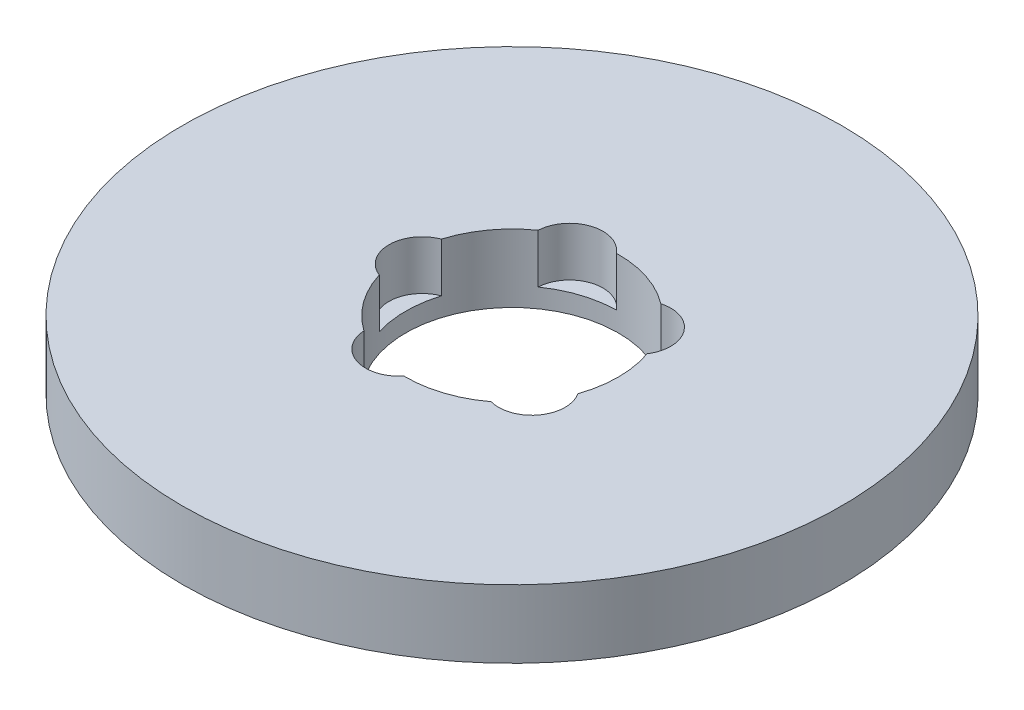
SolidWorks part; units mm, degrees
ref_plane "Front Plane" through (0, 0, 0) normal (0, 0, 1) x (1, 0, 0)
ref_plane "Top Plane" through (0, 0, 0) normal (0, 1, 0) x (1, 0, 0)
ref_plane "Right Plane" through (0, 0, 0) normal (1, 0, 0) x (0, 0, -1)
sketch "Sketch1" plane through (0, 0, 0) normal (0, 1, 0) x (1, 0, 0)
  circle A0 centre (0, 0) radius 77.5
  dimension "FLANGE_OD" = 155
extrude "Boss-Extrude1" add sketch "Sketch1" along normal blind 16
sketch "Sketch2" plane through (0, 0, 0) normal (0, 1, 0) x (1, 0, 0)
  circle A0 centre (0, 0) radius 25
  dimension "BORE_D" = 50
extrude "Cut-Extrude1" cut sketch "Sketch2" along normal through all
sketch "Sketch3" plane through (0, 16, 0) normal (0, 1, 0) x (1, 0, 0)
  circle A0 centre (0, 0) radius 21.1226 construction
  circle A1 centre (-21.1226, 0) radius 7.8149
  dimension "BOLT_D" = 15.6297
  dimension "BOLT_PCD" = 42.2453
extrude "Cut-Extrude2" cut sketch "Sketch3" against normal blind 11.5592
pattern_circular "CirPattern1" count 5 over 360 about axis through (0, 0, 0) along (0, 1, 0) of "Cut-Extrude2"
